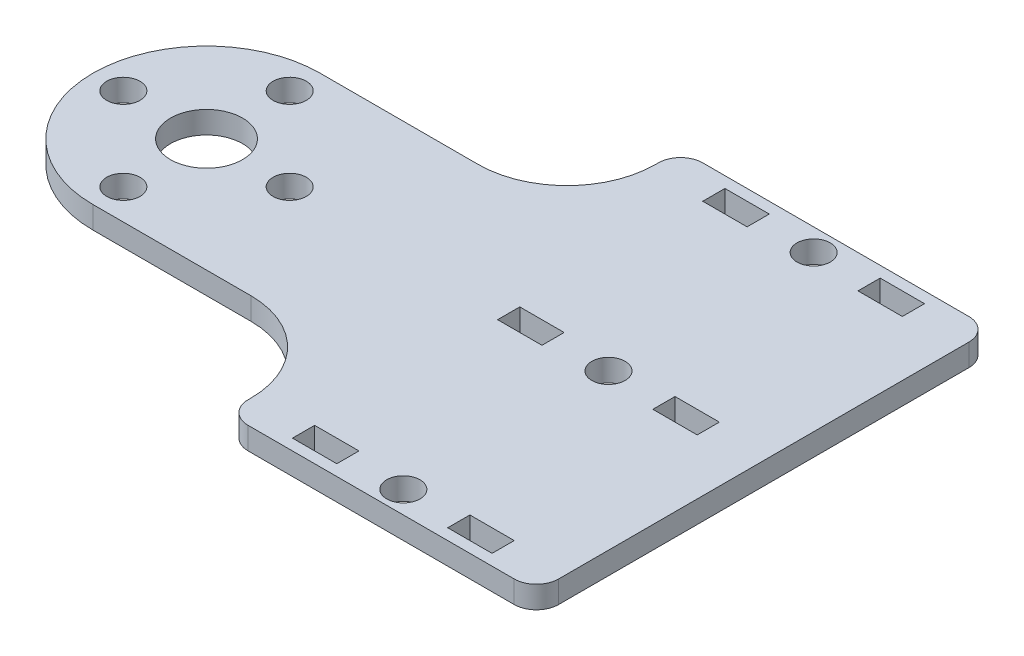
SolidWorks part; units mm, degrees
ref_plane "Front Plane" through (0, 0, 0) normal (0, 0, 1) x (1, 0, 0)
ref_plane "Top Plane" through (0, 0, 0) normal (0, 1, 0) x (1, 0, 0)
ref_plane "Right Plane" through (0, 0, 0) normal (1, 0, 0) x (0, 0, -1)
sketch "Sketch1" plane through (0, 0, 0) normal (0, 1, 0) x (1, 0, 0)
  line L0 (0, 10.25) -> (60.5, 10.25) construction
  line L1 (0, 0) -> (32.5, 0)
  line L2 (0, 0) -> (0, 20.5)
  line L3 (0, 20.5) -> (32.5, 20.5)
  line L4 (60.5, -0.75) -> (60.5, 21.25)
  line L5 (10.25, 10.25) -> (10.25, 20.5) construction
  line L6 (10.25, 10.25) -> (1.2579, 19.2421) construction
  line L7 (10.25, 10.25) -> (1.2579, 1.2579) construction
  line L8 (32.5, 0) -> (32.5, -10.25)
  line L10 (60.5, 21.25) -> (60.5, 30.75)
  line L11 (60.5, 30.75) -> (32.5, 30.75)
  line L12 (32.5, 20.5) -> (32.5, 30.75)
  line L13 (60.5, -10.25) -> (32.5, -10.25)
  line L14 (60.5, -0.75) -> (60.5, -10.25)
  circle A0 centre (10.25, 10.25) radius 3.25
  circle A1 centre (2.75, 10.25) radius 1.5
  circle A2 centre (10.25, 17.75) radius 1.5
  circle A3 centre (17.75, 10.25) radius 1.5
  circle A4 centre (10.25, 2.75) radius 1.5
  dimension "D1" = 3
  dimension "D2" = 7.5
  dimension "D3" = 6.5
  dimension "D4" = 20.5
  dimension "D5" = 10.25
  dimension "D6" = 50.25
  dimension "D7" = 41
  dimension "D8" = 28
extrude "Boss-Extrude1" add sketch "Sketch1" along normal blind 2
fillet "Fillet1" radius 10.25 2 edges at (0, 1, -20.5) (0, 1, 0)
fillet "Fillet2" radius 2 4 edges at (32.5, 1, -30.75) (60.5, 1, -30.75) (60.5, 1, 10.25) (32.5, 1, 10.25)
sketch "Sketch2" plane through (0, 2, 0) normal (0, 1, 0) x (1, 0, 0)
  line L0 (60.5, 10.25) -> (0, 10.25) construction
  line L1 (60.5, -8.25) -> (60.5, 28.75) construction
  line L2 (32.5, 28.75) -> (60.5, 28.75) construction
  line L3 (32.5, 28.75) -> (32.5, 20.5) construction
  line L15 (58.5, 30.75) -> (34.5, 30.75) construction
  line L17 (37.5, 27.75) -> (41.5, 27.75)
  line L18 (37.5, 27.75) -> (37.5, 29.75)
  line L19 (37.5, 29.75) -> (41.5, 29.75)
  line L20 (41.5, 27.75) -> (41.5, 29.75)
  line L21 (37.5, 27.75) -> (41.5, 29.75) construction
  line L22 (37.5, 29.75) -> (41.5, 27.75) construction
  line L23 (55.5, 27.75) -> (51.5, 27.75)
  line L24 (55.5, 27.75) -> (55.5, 29.75)
  line L25 (55.5, 29.75) -> (51.5, 29.75)
  line L26 (51.5, 27.75) -> (51.5, 29.75)
  line L27 (55.5, 27.75) -> (51.5, 29.75) construction
  line L28 (55.5, 29.75) -> (51.5, 27.75) construction
  line L37 (37.5, 9.25) -> (37.5, 11.25)
  line L38 (37.5, 9.25) -> (41.5, 9.25)
  line L39 (41.5, 9.25) -> (41.5, 11.25)
  line L40 (37.5, 11.25) -> (41.5, 11.25)
  line L41 (55.5, 9.25) -> (55.5, 11.25)
  line L42 (55.5, 9.25) -> (51.5, 9.25)
  line L43 (51.5, 9.25) -> (51.5, 11.25)
  line L44 (55.5, 11.25) -> (51.5, 11.25)
  line L53 (37.5, -9.25) -> (37.5, -7.25)
  line L54 (37.5, -9.25) -> (41.5, -9.25)
  line L55 (41.5, -9.25) -> (41.5, -7.25)
  line L56 (37.5, -7.25) -> (41.5, -7.25)
  line L57 (55.5, -9.25) -> (55.5, -7.25)
  line L58 (55.5, -9.25) -> (51.5, -9.25)
  line L59 (51.5, -9.25) -> (51.5, -7.25)
  line L60 (55.5, -7.25) -> (51.5, -7.25)
  circle A3 centre (46.5, 28.75) radius 1.5
  circle A4 centre (46.5, 10.25) radius 1.5
  circle A5 centre (46.5, -8.25) radius 1.5
  point P9 (26.5, 28.75)
  point P10 (53.5, 29.75)
  point P14 (35.5, 28.75)
  point P19 (39.5, 28.75)
  point P24 (53.5, 28.75)
  dimension "D11" = 3
  dimension "D12" = 5
  dimension "D2" = 4
  dimension "D3" = 1
  dimension "D5" = 5
  dimension "D6" = 10
  dimension "D8" = 3
extrude "Cut-Extrude1" cut sketch "Sketch2" against normal blind 2
fillet "Fillet3" radius 8 2 edges at (32.5, 1, 0) (32.5, 1, -20.5)
